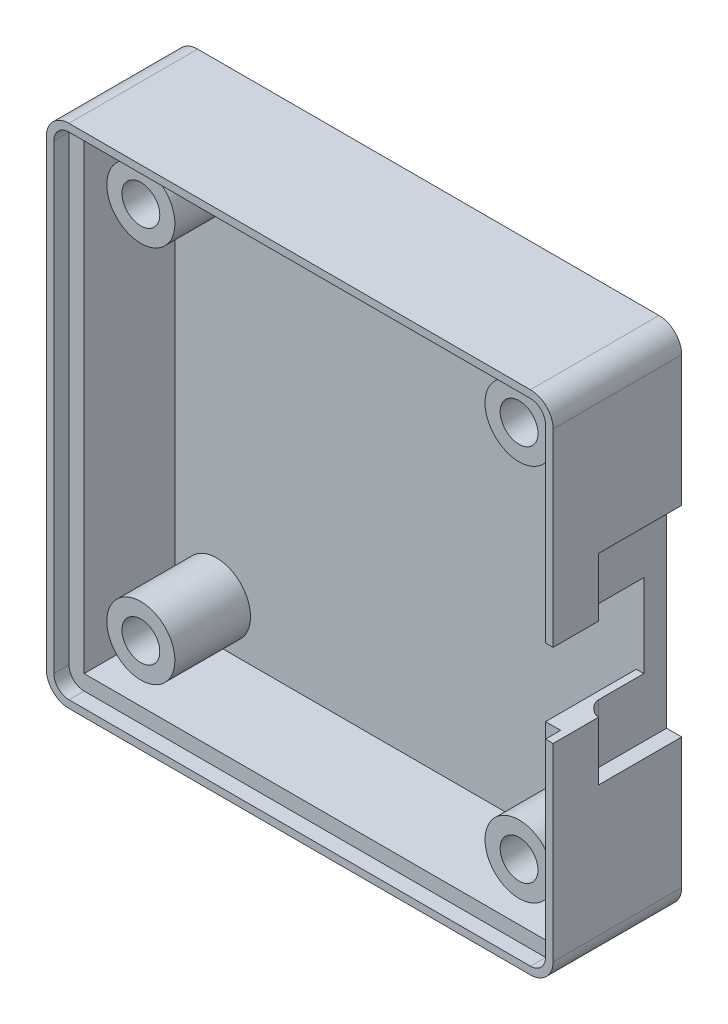
SolidWorks part; units mm, degrees
ref_plane "Front Plane" through (0, 0, 0) normal (0, 0, 1) x (1, 0, 0)
ref_plane "Top Plane" through (0, 0, 0) normal (0, 1, 0) x (1, 0, 0)
ref_plane "Right Plane" through (0, 0, 0) normal (1, 0, 0) x (0, 0, -1)
sketch "Sketch1" plane through (0, 0, 0) normal (0, 0, 1) x (1, 0, 0)
  line L1 (-33.6217, 29.2297) -> (33.3783, 29.2297)
  line L2 (-33.6217, 29.2297) -> (-33.6217, -37.7703)
  line L3 (-33.6217, -37.7703) -> (33.3783, -37.7703)
  line L4 (33.3783, 29.2297) -> (33.3783, -37.7703)
  dimension "D1" = 67
  dimension "D2" = 67
extrude "Boss-Extrude1" add sketch "Sketch1" along normal blind 17
sketch "Sketch2" plane through (0, 0, 17) normal (0, 0, 1) x (1, 0, 0)
  line L0 (33.3783, -37.7703) -> (33.3783, 29.2297) construction
  line L1 (30.3783, 26.2297) -> (-30.6217, 26.2297)
  line L2 (30.3783, 26.2297) -> (30.3783, -34.7703)
  line L3 (30.3783, -34.7703) -> (-30.6217, -34.7703)
  line L4 (-30.6217, 26.2297) -> (-30.6217, -34.7703)
  line L6 (33.3783, 29.2297) -> (-33.6217, 29.2297) construction
  dimension "D1" = 61
  dimension "D2" = 61
  dimension "D3" = 3
  dimension "D4" = 3
extrude "Cut-Extrude1" cut sketch "Sketch2" against normal blind 14
sketch "Sketch3" plane through (0, 0, 0) normal (0, 0, 1) x (1, 0, 0)
  line L0 (33.3783, -37.7703) -> (33.3783, 29.2297) construction
  line L1 (32.3783, 28.2297) -> (-32.6217, 28.2297)
  line L2 (32.3783, 28.2297) -> (32.3783, -36.7703)
  line L3 (32.3783, -36.7703) -> (-32.6217, -36.7703)
  line L4 (-32.6217, 28.2297) -> (-32.6217, -36.7703)
  line L5 (33.3783, 29.2297) -> (-33.6217, 29.2297) construction
  dimension "D1" = 65
  dimension "D2" = 65
  dimension "D3" = 1
  dimension "D4" = 1
extrude "Cut-Extrude2" cut sketch "Sketch3" against normal blind 2 from surface starting at face at (-0.1217, -4.2703, 17)
fillet "Fillet1" radius 3 1 edges at (-33.6217, -37.7703, 8.5)
fillet "Fillet3" radius 2 1 edges at (-32.6217, -36.7703, 16)
fillet "Fillet4" radius 2 1 edges at (-32.6217, 28.2297, 16)
fillet "Fillet5" radius 2 1 edges at (32.3783, 28.2297, 16)
fillet "Fillet6" radius 2 1 edges at (32.3783, -36.7703, 16)
fillet "Fillet7" radius 3 1 edges at (33.3783, -37.7703, 8.5)
fillet "Fillet8" radius 3 1 edges at (33.3783, 29.2297, 8.5)
fillet "Fillet9" radius 3 1 edges at (-33.6217, 29.2297, 8.5)
sketch "Sketch4" plane through (0, 0, 3) normal (0, 0, 1) x (1, 0, 0)
  line L0 (-30.6217, -34.7703) -> (30.3783, -34.7703) construction
  line L1 (30.3783, -34.7703) -> (30.3783, 26.2297) construction
  line L2 (-30.6217, 26.2297) -> (-30.6217, -34.7703) construction
  line L3 (30.3783, 26.2297) -> (-30.6217, 26.2297) construction
  circle A0 centre (24.8783, -29.2703) radius 4.5
  circle A1 centre (24.8783, -29.2703) radius 2.5
  circle A2 centre (-25.1217, -29.2703) radius 4.5
  circle A3 centre (-25.1217, -29.2703) radius 2.5
  circle A4 centre (-25.1217, 20.7297) radius 4.5
  circle A5 centre (-25.1217, 20.7297) radius 2.5
  circle A7 centre (24.8783, 20.7297) radius 4.5
  circle A8 centre (24.8783, 20.7297) radius 2.5
  dimension "D1" = 5.5
  dimension "D3" = 5.5
  dimension "D5" = 5.5
  dimension "D2" = 5.5
  dimension "D4" = 5.5
  dimension "D6" = 5.5
extrude "Boss-Extrude2" add sketch "Sketch4" along normal blind 10
sketch "Sketch5" plane through (0, 0, 3) normal (0, 0, 1) x (1, 0, 0)
  circle A0 centre (24.8783, -29.2703) radius 2.5
  circle A1 centre (-25.1217, -29.2703) radius 2.5
  circle A2 centre (-25.1217, 20.7297) radius 2.5
  circle A3 centre (24.8783, 20.7297) radius 2.5
extrude "Boss-Extrude3" add sketch "Sketch5" along normal blind 5
sketch "Sketch6" plane through (33.3783, 0, 0) normal (1, 0, 0) x (0, 0, -1)
  line L0 (-17, -34.7703) -> (-17, 26.2297) construction
  line L1 (-31, -9.7703) -> (-3, -9.7703)
  line L2 (-31, -9.7703) -> (-31, 1.2297)
  line L3 (-31, 1.2297) -> (-3, 1.2297)
  line L4 (-3, -9.7703) -> (-3, 1.2297)
  line L5 (-31, -9.7703) -> (-3, 1.2297) construction
  line L6 (-31, 1.2297) -> (-3, -9.7703) construction
  line L7 (0, -34.7703) -> (0, 26.2297) construction
  point P0 (-17, -4.2703)
  dimension "D1" = 11
  dimension "D2" = 3
extrude "Cut-Extrude3" cut sketch "Sketch6" against normal blind 6
sketch "Sketch7" plane through (33.3783, 0, 0) normal (1, 0, 0) x (0, 0, -1)
  line L0 (0, -34.7703) -> (0, 26.2297) construction
  line L1 (10.9882, -17.5271) -> (-10.9882, -17.5271)
  line L2 (10.9882, -17.5271) -> (10.9882, 8.9865)
  line L3 (10.9882, 8.9865) -> (-10.9882, 8.9865)
  line L4 (-10.9882, -17.5271) -> (-10.9882, 8.9865)
  line L5 (10.9882, -17.5271) -> (-10.9882, 8.9865) construction
  line L6 (10.9882, 8.9865) -> (-10.9882, -17.5271) construction
  point P0 (0, -4.2703)
extrude "Cut-Extrude4" cut sketch "Sketch7" against normal blind 2
fillet "Fillet12" radius 2 1 edges at (31.3783, 5.1081, 10.9882) conic radius 3
fillet "Fillet13" radius 2 1 edges at (31.3783, -13.6487, 10.9882) conic radius 3
